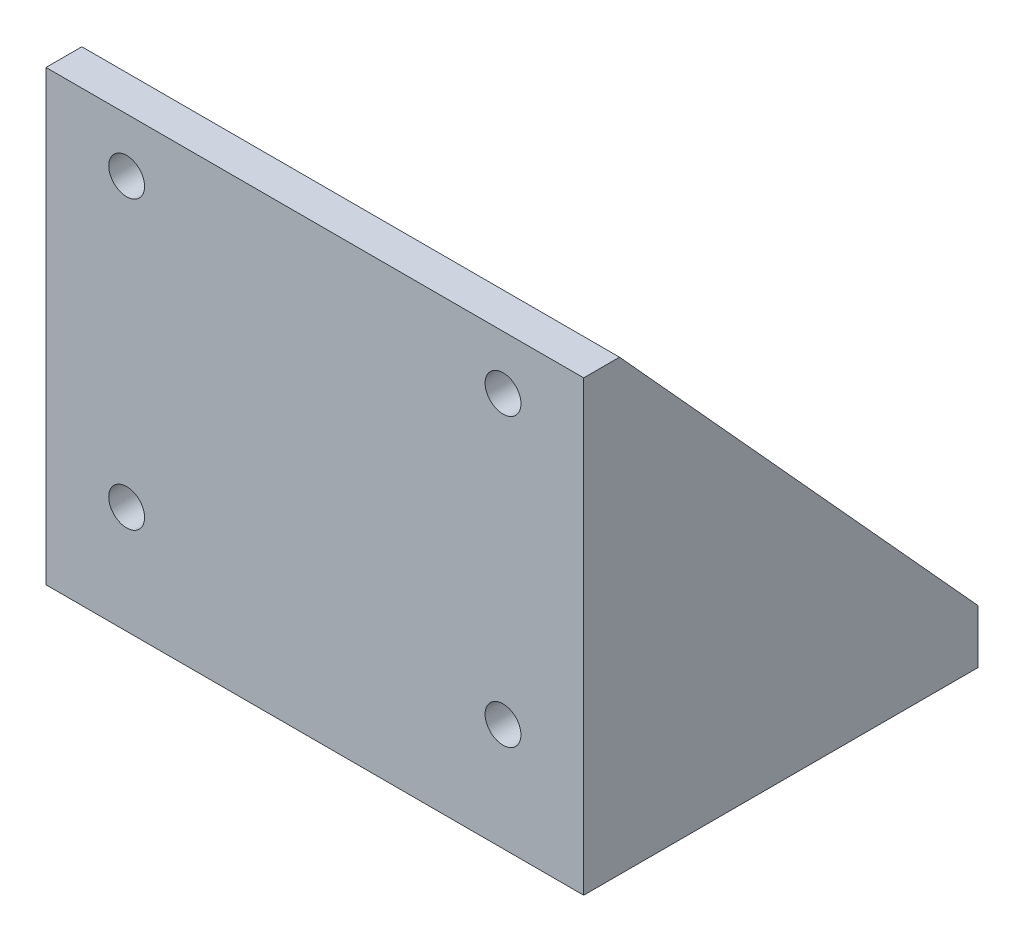
SolidWorks part; units mm, degrees
ref_plane "Plan de face" through (0, 0, 0) normal (0, 0, 1) x (1, 0, 0)
ref_plane "Plan de dessus" through (0, 0, 0) normal (0, 1, 0) x (1, 0, 0)
ref_plane "Plan de droite" through (0, 0, 0) normal (1, 0, 0) x (0, 0, -1)
sketch "Esquisse1" plane through (0, 0, 0) normal (0, 0, 1) x (1, 0, 0)
  line L1 (0, 0) -> (60, 0)
  line L2 (0, 0) -> (0, 6)
  line L3 (0, 6) -> (60, 6)
  line L4 (60, 0) -> (60, 6)
  dimension "D1" = 6
  dimension "D2" = 60
extrude "Boss.-Extru.1" add sketch "Esquisse1" along normal blind 40
sketch "Esquisse2" plane through (0, 6, 0) normal (0, 1, 0) x (1, 0, 0)
  line L0 (30, -40) -> (30, 0) construction
  line L1 (60, -40) -> (0, -40) construction
  line L2 (60, 0) -> (0, 0) construction
  circle A0 centre (30, -20) radius 5
  dimension "D1" = 10
extrude "Enlèv. mat.-Extru.1" cut sketch "Esquisse2" against normal through all both and the other way through all
sketch "Esquisse4" plane through (0, 6, 0) normal (0, 1, 0) x (1, 0, 0)
  line L0 (30, -20) -> (45, -20) construction
  circle A0 centre (45, -20) radius 1.75
  circle A1 centre (22.5, -32.9904) radius 1.75
  circle A2 centre (22.5, -7.0096) radius 1.75
  point P4 (21.4646, -5.6878)
  point P5 (30, -20)
  point P10 (30, -20)
  dimension "D1" = 3.5
  dimension "D2" = 15
  dimension "D3" = 3
extrude "Enlèv. mat.-Extru.3" cut sketch "Esquisse4" against normal through all both and the other way through all
sketch "Esquisse7" plane through (0, 0, 0) normal (0, -1, 0) x (1, 0, 0)
  line L0 (60, 40) -> (60, 0) construction
  line L1 (0, 40) -> (60, 40)
  line L2 (0, 40) -> (0, 44)
  line L3 (0, 44) -> (60, 44)
  line L4 (60, 40) -> (60, 44)
  dimension "D1" = 4
extrude "Boss.-Extru.2" add sketch "Esquisse7" against normal blind 50
sketch "Esquisse8" plane through (60, 0, 0) normal (1, 0, 0) x (0, 0, -1)
  line L0 (0, 6) -> (-40, 50)
  line L1 (-40, 50) -> (-40, 6)
  line L2 (-40, 6) -> (0, 6)
extrude "Boss.-Extru.3" add sketch "Esquisse8" against normal blind 3
extrude "Boss.-Extru.4" add sketch "Esquisse8<2>" along normal blind 3 from vertex starting at point (0, 6, 40)
sketch "Esquisse8<2>" plane through (60, 0, 0) normal (1, 0, 0) x (0, 0, -1) same geometry as "Esquisse8"
sketch "Esquisse9" plane through (0, 0, 40) normal (0, 0, -1) x (-1, 0, 0)
  line L0 (-30, 50) -> (-30, 6) construction
  line L1 (-3, 50) -> (-57, 50) construction
  line L2 (-57, 6) -> (-3, 6) construction
  line L3 (-30, 28) -> (-50.8103, 28) construction
  circle A0 centre (-51, 12) radius 2
  circle A1 centre (-51, 44) radius 2
  circle A2 centre (-9, 44) radius 2
  circle A3 centre (-9, 12) radius 2
  dimension "D1" = 4
  dimension "D2" = 42
  dimension "D3" = 32
extrude "Enlèv. mat.-Extru.4" cut sketch "Esquisse9" against normal through all both and the other way through all
chamfer "Chanfrein1" distance 1 angle 45 4 edges at (7, 12, 40) (7, 44, 40) (49, 44, 40) (49, 12, 40)
